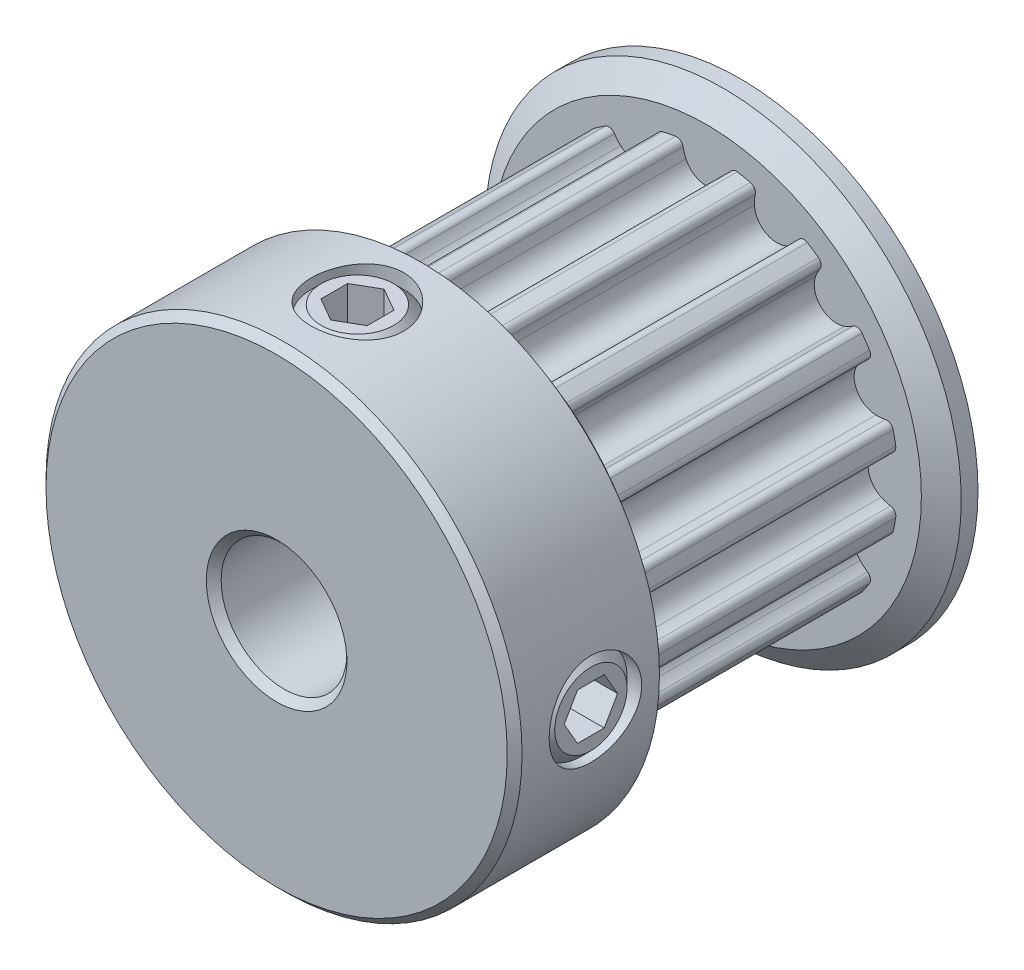
SolidWorks part; units mm, degrees
ref_plane "Front Plane" through (0, 0, 0) normal (0, 0, 1) x (1, 0, 0)
ref_plane "Top Plane" through (0, 0, 0) normal (0, 1, 0) x (1, 0, 0)
ref_plane "Right Plane" through (0, 0, 0) normal (1, 0, 0) x (0, 0, -1)
sketch "Sketch1" plane through (0, 0, 0) normal (0, 0, 1) x (1, 0, 0)
  line L1 (-2.553, 6.1245) -> (2.553, 6.1245) construction
  line L4 (0, 0) -> (0, 6.1245) construction
  line L5 (0, 6.1245) -> (0, 12.0658) construction
  line L6 (0, 7.6455) -> (2.9417, 7.0569) construction
  line L7 (2.9417, 7.0569) -> (3.8741, 6.6682) construction
  line L8 (2.9417, 7.0569) -> (2.553, 6.1245) construction
  line L9 (-2.9417, 7.0569) -> (-2.553, 6.1245) construction
  line L10 (-2.7951, 6.7052) -> (-3.7579, 9.015)
  line L11 (-3.7579, 9.015) -> (3.7579, 9.015)
  line L12 (3.7579, 9.015) -> (2.7951, 6.7052)
  circle A0 centre (0, 0) radius 7.6455 construction
  circle A1 centre (0, 0) radius 9.015 construction
  circle A2 centre (0, 0) radius 7.2645 construction
  arc A3 (-0.7739, 6.6229) -> (0.7739, 6.6229) centre (0, 6.9745) ccw
  arc A4 (-0.7739, 6.6229) -> (-0.8836, 6.9694) centre (0.61, 7.2516) cw
  arc A5 (-2.7951, 6.7052) -> (-1.1695, 7.1697) centre (0, 0) cw
  arc A6 (-0.8836, 6.9694) -> (-1.1695, 7.1697) centre (-1.1292, 6.923) ccw
  arc A7 (2.7951, 6.7052) -> (1.1695, 7.1697) centre (0, 0) ccw
  arc A8 (0.8836, 6.9694) -> (1.1695, 7.1697) centre (1.1292, 6.923) cw
  arc A9 (0.7739, 6.6229) -> (0.8836, 6.9694) centre (-0.61, 7.2516) ccw
  point P6 (0, 20.9083)
  point P11 (0, 7.6455)
  point P13 (0, 9.015)
  point P14 (0, 7.2645)
  dimension "D1" = 8.8425
  dimension "D2" = 4.4203
sketch "Sketch2" plane through (0, 0, 0) normal (1, 0, 0) x (0, 0, -1)
  line L0 (-8.775, 2.3812) -> (8.775, 2.3812)
  line L1 (-8.775, 2.3812) -> (-8.775, 9.015)
  line L2 (-3.29, 9.015) -> (-8.775, 9.015)
  line L3 (-3.925, 2.3813) -> (-3.925, 9.015) construction
  line L4 (-3.925, 9.015) -> (-2.655, 9.015) construction
  line L5 (-2.655, 9.015) -> (-2.655, 7.2645) construction
  line L6 (-2.655, 7.2645) -> (7.505, 7.2645)
  line L7 (7.505, 7.2645) -> (7.505, 9.015) construction
  line L8 (7.505, 9.015) -> (8.775, 9.015) construction
  line L9 (8.775, 9.015) -> (8.775, 2.3812)
  line L10 (-8.775, 0) -> (8.775, 0) construction
  line L11 (8.14, 9.015) -> (7.505, 8.1398)
  line L12 (-2.655, 8.1398) -> (-3.29, 9.015)
  line L14 (-2.655, 8.1398) -> (-2.655, 7.2645)
  line L15 (7.505, 7.2645) -> (7.505, 8.1398)
  line L16 (8.14, 9.015) -> (8.775, 9.015)
  arc A0 (-2.655, 8.1398) -> (-3.29, 9.015) centre (-3.5757, 8.1398) ccw construction
  arc A1 (7.505, 8.1398) -> (8.14, 9.015) centre (8.4257, 8.1398) cw construction
  point P12 (-2.655, 8.1398)
  point P14 (-3.29, 9.015)
  point P20 (7.505, 8.1398)
  point P21 (8.14, 9.015)
  point P25 (7.505, 0)
  point P26 (-2.655, 0)
  dimension "OA" = 17.55
  dimension "Bore" = 4.7625
  dimension "Outside Width" = 11.43
  dimension "Inside Width" = 10.16
revolve "Revolve1" add sketch "Sketch2" angle 360 mid plane about L10
sketch "Sketch3" plane through (0, 0, 0) normal (0, 0, 1) x (1, 0, 0)
  line L6 (3.7579, 9.015) -> (-3.7579, 9.015)
  line L7 (2.7951, 6.7052) -> (3.7579, 9.015)
  line L8 (-3.7579, 9.015) -> (-2.7951, 6.7052)
  line L9 (3.7579, 9.015) -> (-3.7579, 9.015)
  line L10 (2.7951, 6.7052) -> (3.7579, 9.015)
  line L11 (-3.7579, 9.015) -> (-2.7951, 6.7052)
  arc A8 (2.7951, 6.7052) -> (1.1695, 7.1697) centre (0, 0) ccw
  arc A9 (1.1695, 7.1697) -> (0.8836, 6.9694) centre (1.1292, 6.923) ccw
  arc A10 (0.7739, 6.6229) -> (0.8836, 6.9694) centre (-0.61, 7.2516) ccw
  arc A11 (-0.7739, 6.6229) -> (0.7739, 6.6229) centre (0, 6.9745) ccw
  arc A12 (-0.8836, 6.9694) -> (-0.7739, 6.6229) centre (0.61, 7.2516) ccw
  arc A13 (-0.8836, 6.9694) -> (-1.1695, 7.1697) centre (-1.1292, 6.923) ccw
  arc A14 (-1.1695, 7.1697) -> (-2.7951, 6.7052) centre (0, 0) ccw
  arc A15 (2.7951, 6.7052) -> (1.1695, 7.1697) centre (0, 0) ccw
  arc A16 (1.1695, 7.1697) -> (0.8836, 6.9694) centre (1.1292, 6.923) ccw
  arc A17 (0.7739, 6.6229) -> (0.8836, 6.9694) centre (-0.61, 7.2516) ccw
  arc A18 (-0.7739, 6.6229) -> (0.7739, 6.6229) centre (0, 6.9745) ccw
  arc A19 (-0.8836, 6.9694) -> (-0.7739, 6.6229) centre (0.61, 7.2516) ccw
  arc A20 (-0.8836, 6.9694) -> (-1.1695, 7.1697) centre (-1.1292, 6.923) ccw
  arc A21 (-1.1695, 7.1697) -> (-2.7951, 6.7052) centre (0, 0) ccw
  dimension "D1" = 0
extrude "Cut-Extrude1" cut sketch "Sketch3" against normal up to vertex (7.505 mm away) from vertex up to point (0, 7.2645, -7.505) starting at point (0, 7.2645, 2.655)
pattern_circular "CirPattern1" count 16 over 360 about axis through (0, 0, 8.775) along (0, 0, 1) of "Cut-Extrude1"
sketch "Sketch4" plane through (0, 0, 0) normal (1, 0, 0) x (0, -1, 0)
  line L0 (0, -2.655) -> (0, -8.775) construction
  line L1 (-2.3812, -8.775) -> (2.3812, -8.775) construction
  line L2 (8.1398, -2.655) -> (-8.1398, -2.655) construction
  circle A0 centre (0, -5.715) radius 1.7526
extrude "Cut-Extrude2" cut sketch "Sketch4" along normal through all
ref_plane "Plane1" through (0, 0, 5.715) normal (0, 0, 1) x (1, 0, 0)
sketch "Sketch5" plane through (0, 0, 5.715) normal (0, 0, 1) x (1, 0, 0)
  line L0 (0, 0) -> (0, 9.015) construction
  line L1 (2.3812, -1.3716) -> (2.3812, 0)
  line L2 (2.7622, -1.7526) -> (8.462, -1.7526)
  line L3 (2.3812, 0) -> (9.015, 0) construction
  line L4 (2.3812, 0) -> (8.843, 0)
  line L5 (8.843, 0) -> (8.843, -1.3716)
  line L6 (2.7622, -1.7526) -> (2.3812, -1.3716)
  line L7 (8.843, -1.3716) -> (8.462, -1.7526)
  circle A0 centre (0, 0) radius 9.015 construction
  circle A1 centre (0, 0) radius 2.3812 construction
  point P2 (2.3812, -1.7526)
  point P11 (8.843, -1.7526)
revolve "Revolve2" add sketch "Sketch5" angle 360 mid plane about L4
sketch "Sketch6" plane through (8.843, 5.3841, 0) normal (-1, 0, 0) x (0, -1, 0)
  line L1 (5.3841, 6.7269) -> (4.5078, 6.2209)
  line L2 (4.5078, 6.2209) -> (4.5078, 5.2091)
  line L3 (4.5078, 5.2091) -> (5.3841, 4.7031)
  line L4 (5.3841, 4.7031) -> (6.2604, 5.2091)
  line L5 (6.2604, 5.2091) -> (6.2604, 6.2209)
  line L6 (6.2604, 6.2209) -> (5.3841, 6.7269)
  circle A0 centre (5.3841, 5.715) radius 0.8763 construction
  dimension "D1" = 1.7526
extrude "Cut-Extrude3" cut sketch "Sketch6" along normal blind 1.3144
pattern_circular "CirPattern3" count 2 over 90 about axis through (0, 0, 8.775) along (0, 0, 1) of "Cut-Extrude2", "Revolve2", "Cut-Extrude3"
chamfer "Chamfer1" distance 0.2807 angle 45 2 edges at (2.3812, 0, 8.775) (9.015, 0, 8.775)
ref_axis "Center Axis 1" through (0, 0, -8.775) along (0, 0, 1)
ref_plane "Contact Plane 1" through (0, 0, 8.775) normal (0, 0, 1) x (1, 0, 0)
ref_plane "Contact Plane 2" through (0, 0, -8.775) normal (0, 0, -1) x (-1, 0, 0)
equation "\"D2@Sketch1\"= \"D1@Sketch1\" / 2"
equation "\"D1@Sketch6\" = \"Set Screw@Sketch4\" / 2"
equation "\"D1@Cut-Extrude3\" = \"D1@Sketch6\"*.75"
